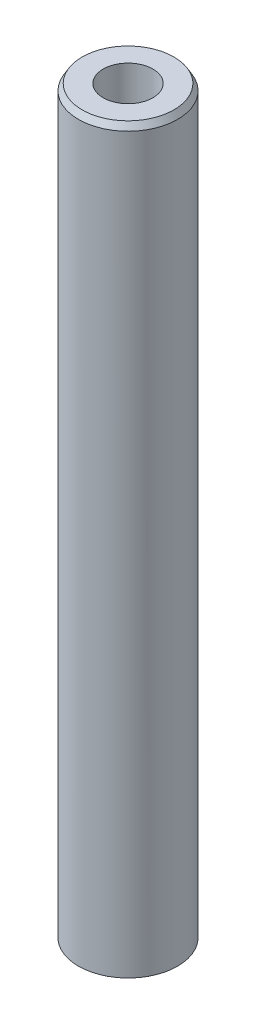
SolidWorks part; units mm, degrees
ref_plane "Front Plane" through (0, 0, 0) normal (0, 0, 1) x (1, 0, 0)
ref_plane "Top Plane" through (0, 0, 0) normal (0, 1, 0) x (1, 0, 0)
ref_plane "Right Plane" through (0, 0, 0) normal (1, 0, 0) x (0, 0, -1)
sketch "Sketch1" plane through (0, 0, 0) normal (0, 1, 0) x (1, 0, 0)
  circle A0 centre (0, 0) radius 40
  dimension "SHAFT_OD" = 80
extrude "Boss-Extrude1" add sketch "Sketch1" along normal blind 600
sketch "Sketch2" plane through (0, 0, 0) normal (0, 1, 0) x (1, 0, 0)
  circle A0 centre (0, 0) radius 20.0903
  dimension "BORE_D" = 40.1807
extrude "Cut-Extrude1" cut sketch "Sketch2" along normal through all
chamfer "Chamfer1" distance 5.1635 angle 30 2 edges at (0, 600, 40) (0, 0, 40) first distance on face at (0, 600, 40) first distance on face at (0, 0, 20.0903)
